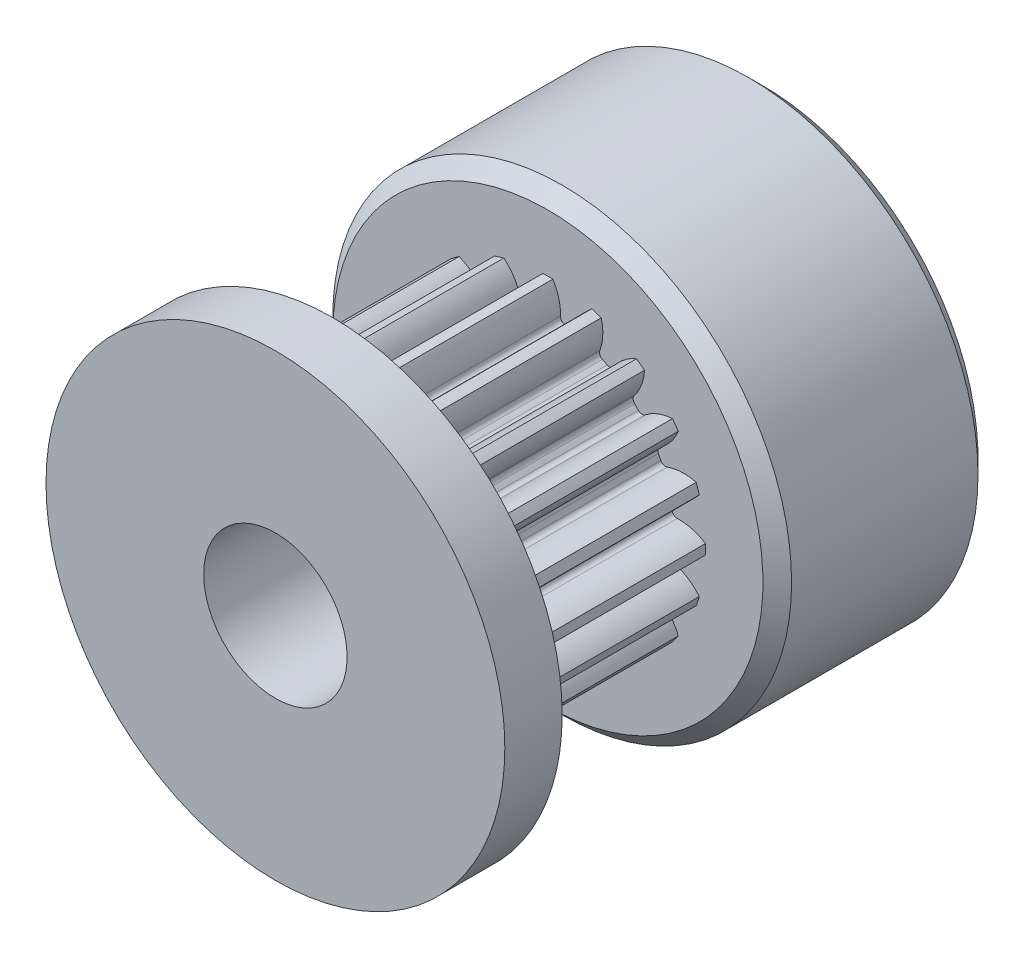
SolidWorks part; units mm, degrees
material "ABS"
ref_plane "Plane1" through (0, 0, 0) normal (0, 0, 1) x (1, 0, 0)
ref_plane "Plane2" through (0, 0, 0) normal (0, 1, 0) x (1, 0, 0)
ref_plane "Plane3" through (0, 0, 0) normal (1, 0, 0) x (0, 0, -1)
sketch "Esquisse1" plane through (0, 0, 0) normal (0, 0, 1) x (1, 0, 0)
  circle A0 centre (0, 0) radius 1.15
  dimension "D1" = 2.3
extrude "Base-Extrusion" add sketch "Esquisse1" along normal blind 2.5
sketch "Parametres" plane through (0, 0, 2.5) normal (0, 0, 1) x (1, 0, 0)
  line L0 (-33.4711, 41.7411) -> (-13.4711, 41.7411)
  line L1 (-33.4711, 34.0759) -> (-32.9711, 34.0759)
  line L2 (-33.4711, 23.0892) -> (-13.4711, 23.0892)
  line L3 (-33.4711, -2.6579) -> (-33.1221, -2.6579)
  line L4 (-38.9094, -12.5583) -> (-35.7678, -12.5583)
  line L5 (-48.8826, -19.2556) -> (-43.8826, -19.2556)
  line L6 (-48.8826, -29.9283) -> (-43.3826, -29.9283)
  line L7 (-48.8826, -38.2322) -> (-44.5076, -38.2322)
  line L8 (-48.8826, -45.1309) -> (-44.1841, -45.1309)
  line L9 (-48.8826, -60.7647) -> (-48.0972, -60.7647)
  line L10 (-48.8826, -76.1039) -> (-48.0045, -76.1039)
  line L11 (-48.8826, -88.0795) -> (-48.3359, -88.0795)
  line L12 (-48.8826, -98.8973) -> (-48.5351, -98.8973)
  line L13 (16.9123, -61.9871) -> (25.9123, -61.9871)
  line L14 (18.5152, -81.0212) -> (29.2231, -81.0212)
  line L15 (18.5152, -96.0481) -> (22.1346, -96.0481)
  line L16 (-33.4711, 13.8609) -> (-26.8711, 13.8609)
sketch "Esquisse3" plane through (0, 0, 0) normal (0, 0, 1) x (1, 0, 0)
  line L0 (0, 0) -> (0, 29.3764) construction
  line L1 (-0.6844, 4.3211) -> (0, 0)
  line L2 (0, 0) -> (0.6844, 4.3211)
  line L3 (0, 0) -> (0.4384, 4.678) construction
  line L4 (0, 0) -> (0.1737, 5.4973) construction
  line L5 (0, 0) -> (0.3923, 4.9846) construction
  arc A0 (0.1737, 5.4973) -> (0.4268, 4.3541) centre (-1.2732, 4.5773) cw
  arc A1 (-0.1737, 5.4973) -> (-0.4268, 4.3541) centre (1.2732, 4.5773) ccw
  arc A2 (0.6844, 4.3211) -> (0.4268, 4.3541) centre (0, 0) ccw
  arc A3 (-0.6844, 4.3211) -> (-0.4268, 4.3541) centre (0, 0) cw
  arc A4 (0.1737, 5.4973) -> (-0.1737, 5.4973) centre (0, 0) ccw
  dimension "D4" = 18
  dimension "D5" = 4.6985
  dimension "D6" = 5
  dimension "D1" = 5.5
  dimension "D2" = 5.354
  dimension "D3" = 4.5
  dimension "D7" = 1.81
  dimension "D8" = 4.375
extrude "Boss.-Extru.1" add sketch "Esquisse3" along normal blind 7.5
fillet "Congé1" radius 0.175 2 edges at (0.4268, 4.3541, 3.75) (-0.4268, 4.3541, 3.75)
ref_axis "Axe1" through (0, 0, 57.5) along (0, 0, -1)
pattern_circular "Répétition circulaire4" count 20 every 18 about axis through (0, 0, 57.5) along (0, 0, -1) of "Boss.-Extru.1", "Congé1"
sketch "Sketch2" plane through (0, 0, 7.5) normal (0, 0, 1) x (1, 0, 0)
  circle A0 centre (0, 0) radius 8
  dimension "D1" = 16
extrude "Boss-Extrude1" add sketch "Sketch2" along normal blind 2 contours A0
sketch "Sketch3" plane through (0, 0, 0) normal (0, 0, -1) x (-1, 0, 0)
  circle A0 centre (0, 0) radius 8
extrude "Boss-Extrude2" add sketch "Sketch3" along normal blind 7.5
sketch "Sketch4" plane through (0, 0, -7.5) normal (0, 0, -1) x (-1, 0, 0)
  circle A0 centre (0, 0) radius 2.5
  dimension "D1" = 5
extrude "Cut-Extrude1" cut sketch "Sketch4" against normal through all
chamfer "Chamfer1" distance 0.5 angle 45 2 edges at (-8, 0, 0) (-8, 0, -7.5)
sketch "Sketch6" plane through (0, 0, 0) normal (0, 1, 0) x (1, 0, 0)
  circle A0 centre (0, 3.75) radius 2
  dimension "D1" = 4
  dimension "D2" = 3.75
extrude "Cut-Extrude2" cut sketch "Sketch6" against normal through all
sketch "Sketch7" plane through (0, 0, 0) normal (1, 0, 0) x (0, 0, -1)
  circle A0 centre (3.75, 0) radius 2
  dimension "D1" = 4
  dimension "D2" = 3.75
extrude "Cut-Extrude3" cut sketch "Sketch7" against normal through all
equation "\"PI@Parametres\" = 3.141592654"
equation "\"Alpha_rad@Parametres\" = \"Alpha@Parametres\"*\"PI@Parametres\"/180"
equation "\"R@Parametres\" = \"Z@Parametres\"*\"m@Parametres\"/2"
equation "\"RT@Parametres\" = \"R@Parametres\"+\"m@Parametres\""
equation "\"RP@Parametres\" = \"R@Parametres\"-1.25*\"m@Parametres\""
equation "\"Rb@Parametres\" = \"R@Parametres\"*cos(\"Alpha_rad@Parametres\")"
equation "\"E@Parametres\" = \"PI@Parametres\"*\"R@Parametres\"/\"Z@Parametres\""
equation "\"Eb@Parametres\" = \"Rb@Parametres\"*((\"PI@Parametres\"*\"m@Parametres\"/(2*\"R@Parametres\"))+2*(tan(\"Alpha_rad@Parametres\")-\"Alpha_rad@Parametres\"))"
equation "\"As@Parametres\" = atn(sqr(\"RT@Parametres\"*\"RT@Parametres\"-\"Rb@Parametres\"*\"Rb@Parametres\")/\"Rb@Parametres\")"
equation "\"Et@Parametres\" = \"RT@Parametres\"*((\"E@Parametres\"/\"R@Parametres\")+2*(tan(\"Alpha_rad@Parametres\")-\"Alpha_rad@Parametres\"-tan(\"As@Parametres\")+\"As@Parametres\"))"
equation "\"Ap@Parametres\" = (\"E@Parametres\"/\"R@Parametres\")*180/\"PI@Parametres\""
equation "\"Ab@Parametres\" = (\"Eb@Parametres\"/\"Rb@Parametres\")*180/\"PI@Parametres\""
equation "\"At@Parametres\" = (\"Et@Parametres\"/\"RT@Parametres\")*180/\"PI@Parametres\""
equation "\"D7@Esquisse3\" = \"At@Parametres\"/2"
equation "\"D3@Esquisse3\"=\"Ap@Parametres\"/2"
equation "\"D2@Esquisse3\"=\"Ab@Parametres\"/2"
equation "\"D5@Esquisse3\"=\"Rb@Parametres\""
equation "\"D6@Esquisse3\"=\"R@Parametres\""
equation "\"D1@Esquisse3\"=\"RT@Parametres\""
equation "\"D4@Esquisse3\" = \"Ap@Parametres\"*2"
equation "\"D1@Congé1\" = 0.35*\"m@Parametres\""
equation "\"D2@Répétition circulaire4\" = \"Ap@Parametres\"*2"
equation "\"D1@Répétition circulaire4\" = \"Z@Parametres\""
equation "\"D8@Esquisse3\" = \"RP@Parametres\""
